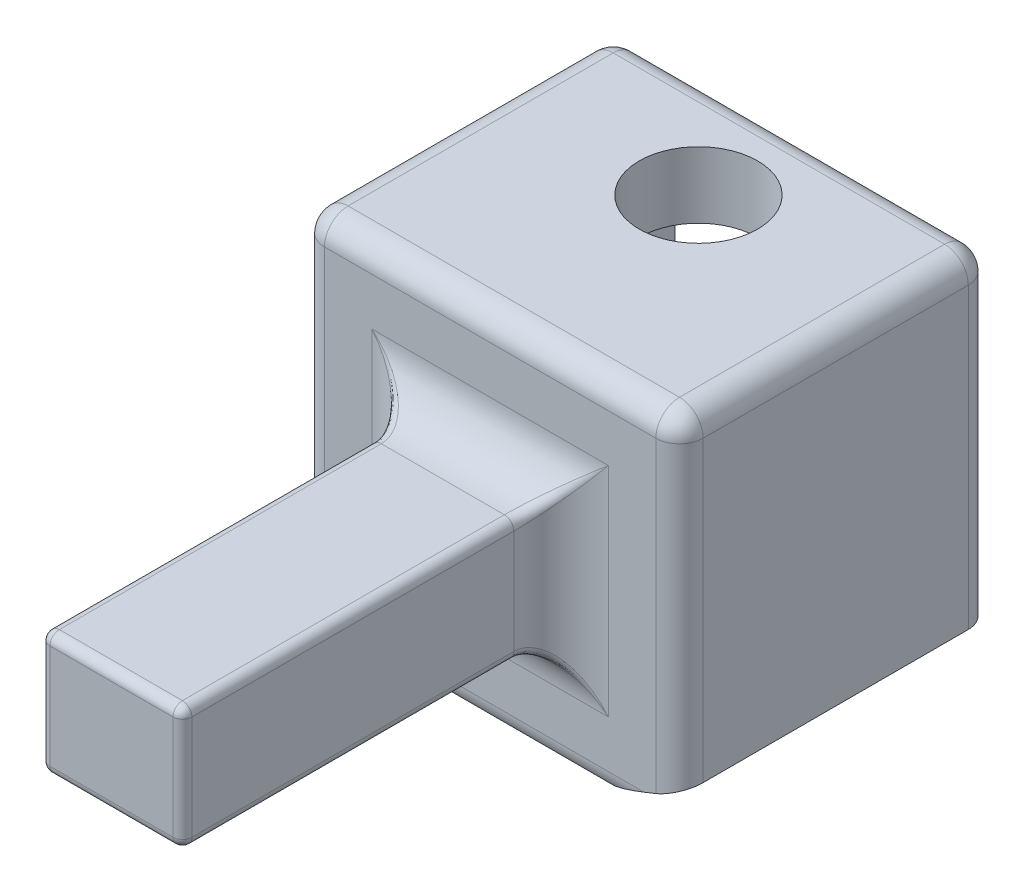
SolidWorks part; units mm, degrees
ref_plane "Front Plane" through (0, 0, 0) normal (0, 0, 1) x (1, 0, 0)
ref_plane "Top Plane" through (0, 0, 0) normal (0, 1, 0) x (1, 0, 0)
ref_plane "Right Plane" through (0, 0, 0) normal (1, 0, 0) x (0, 0, -1)
sketch "Sketch1" plane through (0, 0, 0) normal (0, 0, 1) x (1, 0, 0)
  line L0 (-4.445, -3.81) -> (4.445, -3.81)
  line L1 (-5.08, 4.826) -> (5.08, 4.826)
  line L2 (-5.08, 4.826) -> (-5.08, -4.826)
  line L3 (-5.08, -4.826) -> (5.08, -4.826)
  line L4 (5.08, 4.826) -> (5.08, -4.826)
  line L5 (-5.08, 4.826) -> (5.08, -4.826) construction
  line L6 (-5.08, -4.826) -> (5.08, 4.826) construction
  line L7 (4.445, -3.81) -> (4.445, -1.016)
  line L8 (4.445, -1.016) -> (3.429, -1.016)
  line L9 (3.429, -1.016) -> (3.429, 3.048)
  line L10 (3.429, 3.048) -> (-3.429, 3.048)
  line L11 (-3.429, 3.048) -> (-3.429, -1.016)
  line L12 (-3.429, -1.016) -> (-4.445, -1.016)
  line L13 (-4.445, -1.016) -> (-4.445, -3.81)
  point P5 (0, 3.048)
  point P7 (0, 0)
  dimension "D1" = 10.16
  dimension "D2" = 9.652
  dimension "D3" = 1.016
  dimension "D4" = 6.858
  dimension "D5" = 4.064
  dimension "D6" = 6.858
  dimension "D7" = 8.89
extrude "Boss-Extrude1" add sketch "Sketch1" along normal blind 7.112
sketch "Sketch2" plane through (0, 4.826, 0) normal (0, 1, 0) x (1, 0, 0)
  line L1 (5.08, 0) -> (-5.08, 0) construction
  circle A0 centre (0, -2.794) radius 1.5875
  dimension "D1" = 3.175
  dimension "D2" = 2.794
extrude "Cut-Extrude1" cut sketch "Sketch2" against normal through all both and the other way through all
sketch "Sketch3" plane through (0, 0, 7.112) normal (0, 0, 1) x (1, 0, 0)
  line L1 (-5.08, 4.826) -> (5.08, 4.826)
  line L2 (-5.08, 4.826) -> (-5.08, -4.826)
  line L3 (-5.08, -4.826) -> (5.08, -4.826)
  line L4 (5.08, 4.826) -> (5.08, -4.826)
sketch "Sketch7" plane through (0, 0, 7.112) normal (0, 0, 1) x (1, 0, 0)
  line L0 (-5.08, 4.826) -> (5.08, 4.826)
  line L1 (5.08, 4.826) -> (5.08, -4.826)
  line L2 (5.08, -4.826) -> (-5.08, -4.826)
  line L3 (-5.08, -4.826) -> (-5.08, 4.826)
extrude "Boss-Extrude3" add sketch "Sketch7" along normal blind 1.27
fillet "Fillet1" radius 0.635 3 edges at (-5.08, 0, 0) (0, 4.826, 0) (5.08, 0, 0)
fillet "Fillet3" radius 0.635 13 edges at (-5.08, 4.826, 4.5085) (5.08, 4.826, 4.5085) (-5.08, -4.826, 4.5085) (5.08, -4.826, 4.5085) (-4.894, 4.64, 0.186) (4.894, 4.64, 0.186) (-4.894, -4.826, 0.186) (0, -4.826, 0) (4.894, -4.826, 0.186) (0, 4.826, 8.382) (5.08, 0, 8.382) (0, -4.826, 8.382) (-5.08, 0, 8.382)
fillet "Fillet4" radius 0.381 2 edges at (-3.429, -1.016, 3.556) (3.429, -1.016, 3.556)
sketch "Sketch11" plane through (4.445, 0, 0) normal (-1, 0, 0) x (0, 0, 1)
  line L0 (0, -3.81) -> (5.08, -3.81)
  line L1 (5.08, -3.81) -> (5.08, -4.064)
  line L2 (0, -3.81) -> (0, -4.826)
  line L3 (0, -4.826) -> (10.16, -4.826)
  line L4 (7.747, -4.826) -> (0.635, -4.826) construction
  line L5 (10.16, -4.826) -> (5.08, -4.064)
  dimension "D1" = 0.254
  dimension "D2" = 5.08
  dimension "D3" = 10.16
extrude "Cut-Extrude3" cut sketch "Sketch11" against normal through all both and the other way through all
fillet "Fillet9" radius 0.254 3 edges at (0, -3.81, 7.112) (-4.445, -3.81, 6.096) (4.445, -3.81, 6.096)
sketch "Sketch13" plane through (0, 0, 5.08) normal (0, 0, -1) x (-1, 0, 0)
  line L0 (-5.08, -3.81) -> (-5.08, -4.826)
  line L1 (-5.08, -4.826) -> (-2.54, -4.826)
  line L2 (5.08, -4.826) -> (-5.08, -4.826) construction
  line L3 (-4.445, -3.81) -> (-4.445, -4.064) construction
  line L4 (-5.08, -4.064) -> (5.08, -4.064) construction
  line L5 (-5.08, -3.81) -> (-2.54, -4.826)
  line L6 (5.08, -3.81) -> (5.08, -4.826)
  line L7 (5.08, -4.826) -> (2.032, -4.826)
  line L8 (4.318, -3.81) -> (4.318, -4.064) construction
  line L9 (5.08, -3.81) -> (2.032, -4.826)
extrude "Cut-Extrude7" cut sketch "Sketch13" against normal through all
sketch "Sketch14" plane through (0, 0, 8.382) normal (0, 0, 1) x (1, 0, 0)
  line L8 (-1.905, 1.651) -> (-1.905, -1.651)
  line L9 (-1.905, 1.651) -> (-1.905, -1.651)
  line L10 (-1.905, -1.651) -> (1.905, -1.651)
  line L11 (-1.905, -1.651) -> (1.905, -1.651)
  line L12 (1.905, -1.651) -> (1.905, 1.651)
  line L13 (1.905, -1.651) -> (1.905, 1.651)
  line L14 (1.905, 1.651) -> (-1.905, 1.651)
  line L15 (1.905, 1.651) -> (-1.905, 1.651)
  dimension "D1" = 2.54
extrude "Boss-Extrude4" add sketch "Sketch14" along normal blind 10.16
fillet "Fillet14" radius 1.27 4 edges at (-1.905, 0, 8.382) (0, -1.651, 8.382) (1.905, 0, 8.382) (0, 1.651, 8.382)
fillet "Fillet15" radius 0.254 12 edges at (2.277, -2.023, 8.754) (-2.277, -2.023, 8.754) (-2.277, 2.023, 8.754) (2.277, 2.023, 8.754) (1.905, 0, 18.542) (1.905, -1.651, 14.097) (-1.905, 0, 18.542) (0, -1.651, 18.542) (0, 1.651, 18.542) (-1.905, -1.651, 14.097) (-1.905, 1.651, 14.097) (1.905, 1.651, 14.097)
